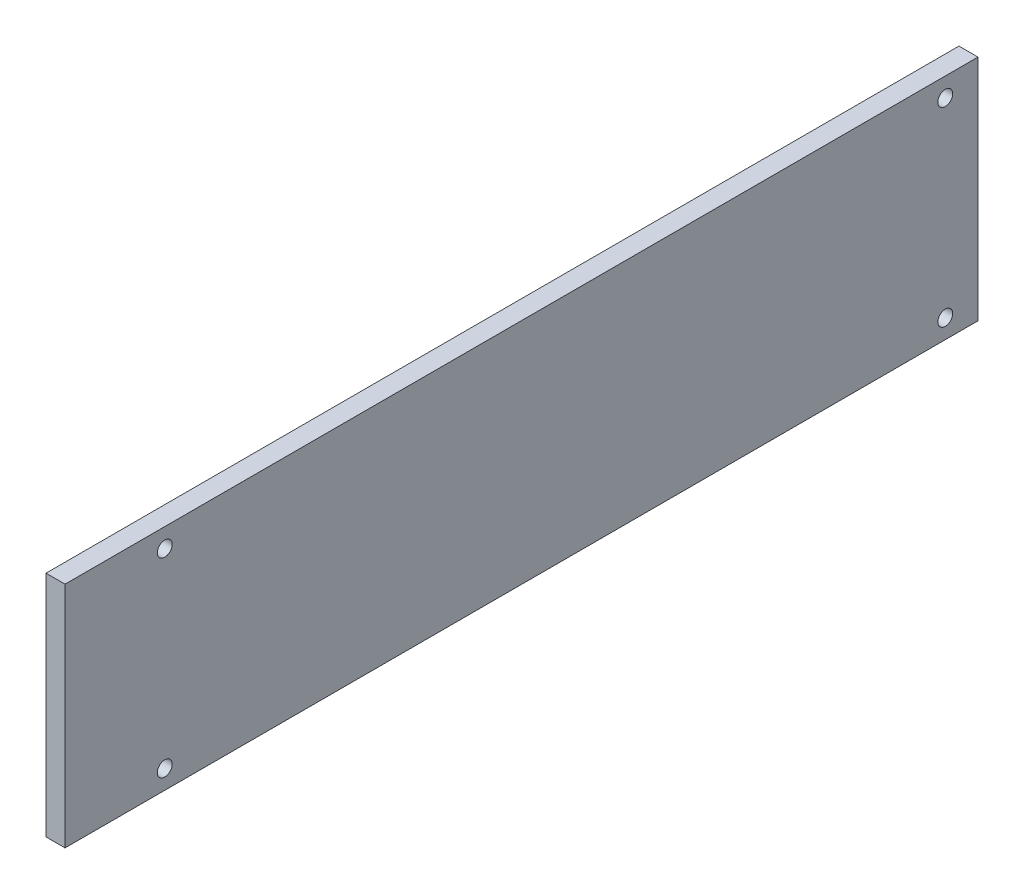
SolidWorks part; units mm, degrees
material "6061-T6 (SS)"
ref_plane "Front Plane" through (0, 0, 0) normal (0, 0, 1) x (1, 0, 0)
ref_plane "Top Plane" through (0, 0, 0) normal (0, 1, 0) x (1, 0, 0)
ref_plane "Right Plane" through (0, 0, 0) normal (1, 0, 0) x (0, 0, -1)
sketch "Sketch1" plane through (0, 0, 0) normal (1, 0, 0) x (0, 0, -1)
  line L1 (-152.273, 38.1) -> (152.273, 38.1)
  line L2 (-152.273, 38.1) -> (-152.273, -38.1)
  line L3 (-152.273, -38.1) -> (152.273, -38.1)
  line L4 (152.273, 38.1) -> (152.273, -38.1)
  line L5 (-152.273, 38.1) -> (152.273, -38.1) construction
  line L6 (-152.273, -38.1) -> (152.273, 38.1) construction
  point P0 (0, 0)
  dimension "D1" = 76.2
  dimension "D2" = 304.546
extrude "Boss-Extrude1" add sketch "Sketch1" along normal blind 6.35
sketch "Sketch2" plane through (6.35, 0, 0) normal (1, 0, 0) x (0, 0, -1)
  line L0 (152.273, -38.1) -> (152.273, 38.1) construction
  line L1 (-118.999, 31.75) -> (141.351, 31.75) construction
  line L2 (-118.999, 31.75) -> (-118.999, -31.75) construction
  line L3 (-118.999, -31.75) -> (141.351, -31.75) construction
  line L4 (141.351, 31.75) -> (141.351, -31.75) construction
  line L5 (-118.999, 31.75) -> (141.351, -31.75) construction
  line L6 (-118.999, -31.75) -> (141.351, 31.75) construction
  line L7 (-152.273, 38.1) -> (-152.273, -38.1) construction
  point P0 (11.176, 0)
  point P7 (0, 0)
  dimension "D1" = 10.922
  dimension "D2" = 33.274
  dimension "D3" = 63.5
hole_wizard "#10 Clearance Hole1" positions "Sketch3" profile "Sketch4" hole size "#10" standard "ANSI Inch" end condition through all
sketch "Sketch3" plane through (6.35, 0, 0) normal (1, 0, 0) x (0, 0, -1)
  point P0 (-118.999, 31.75)
  point P3 (-118.999, -31.75)
  point P6 (141.351, -31.75)
  point P9 (141.351, 31.75)
sketch "Sketch4" plane through (6.35, 31.75, 118.999) normal (0, 1, 0) x (0, 0, -1)
  line L0 (0, 0) -> (0, 6.35)
  line L1 (0, 6.35) -> (2.4892, 6.35)
  line L2 (2.4892, 6.35) -> (2.4892, 0)
  line L5 (2.4892, 0) -> (0, 0)
  line L11 (0, -6.35) -> (0, 107.95) construction
  dimension "Thru Hole Dia." = 4.9784
  dimension "Thru Hole Depth" = 6.35
